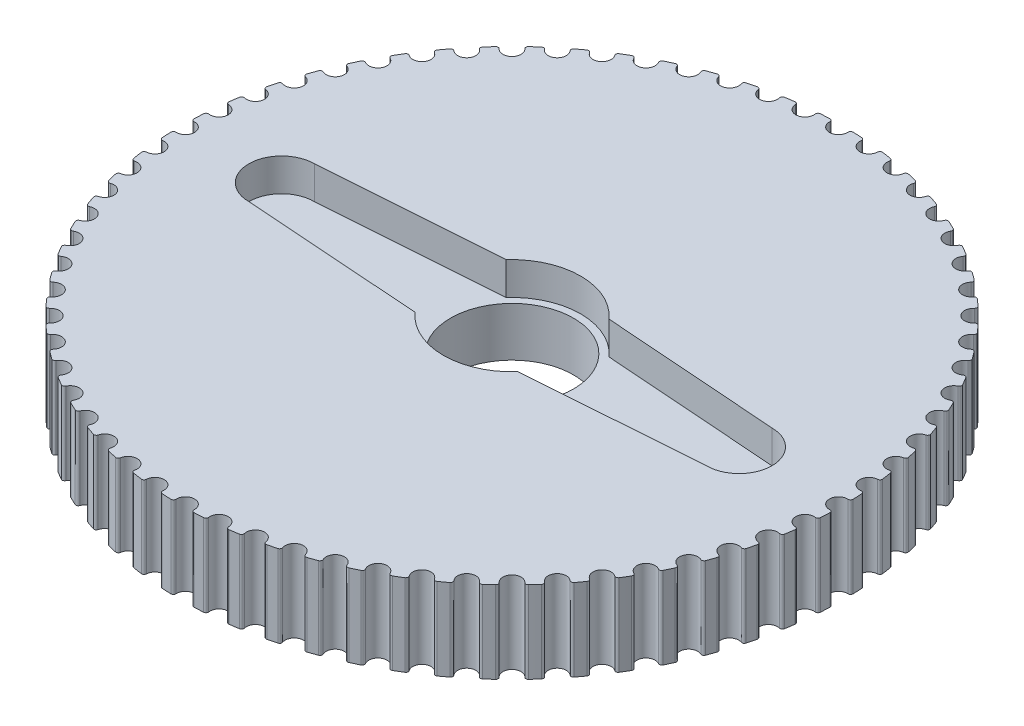
SolidWorks part; units mm, degrees
ref_plane "Front Plane" through (0, 0, 0) normal (0, 0, 1) x (1, 0, 0)
ref_plane "Top Plane" through (0, 0, 0) normal (0, 1, 0) x (1, 0, 0)
ref_plane "Right Plane" through (0, 0, 0) normal (1, 0, 0) x (0, 0, -1)
sketch "Sketch1" plane through (0, 0, 0) normal (0, 1, 0) x (1, 0, 0)
  line L1 (19.37, 0) -> (20.12, 0) construction
  arc A0 (1.2648, 20.0802) -> (0.7095, 20.1075) centre (0, 0) ccw
  arc A2 (0, 19.37) -> (0.5544, 19.9506) centre (0, 19.925) ccw
  arc A3 (1.4038, 19.9089) -> (1.8986, 19.2767) centre (1.953, 19.8291) ccw
  arc A4 (0.7095, 20.1075) -> (0.5544, 19.9506) centre (0.7042, 19.9576) ccw
  arc A5 (1.4038, 19.9089) -> (1.2648, 20.0802) centre (1.2553, 19.9305) ccw
  arc A6 (3.2269, 19.8595) -> (2.677, 19.9411) centre (0, 0) ccw
  arc A7 (1.8986, 19.2767) -> (2.5072, 19.8002) centre (1.953, 19.8291) ccw
  arc A8 (3.3484, 19.6755) -> (3.7789, 18.9978) centre (3.8872, 19.5421) ccw
  arc A9 (2.677, 19.9411) -> (2.5072, 19.8002) centre (2.657, 19.7924) ccw
  arc A10 (3.3484, 19.6755) -> (3.2269, 19.8595) centre (3.2028, 19.7115) ccw
  arc A11 (5.1579, 19.4476) -> (4.6187, 19.5827) centre (0, 0) ccw
  arc A12 (3.7789, 18.9978) -> (4.4359, 19.4591) centre (3.8872, 19.5421) ccw
  arc A13 (5.2608, 19.2525) -> (5.6228, 18.5359) centre (5.7839, 19.067) ccw
  arc A14 (4.6187, 19.5827) -> (4.4359, 19.4591) centre (4.5842, 19.4367) ccw
  arc A15 (5.2608, 19.2525) -> (5.1579, 19.4476) centre (5.1195, 19.3026) ccw
  arc A16 (7.0393, 18.8484) -> (6.5159, 19.0357) centre (0, 0) ccw
  arc A17 (5.6228, 18.5359) -> (6.3219, 18.9306) centre (5.7839, 19.067) ccw
  arc A18 (7.1226, 18.6442) -> (7.4126, 17.8955) centre (7.625, 18.4083) ccw
  arc A19 (6.5159, 19.0357) -> (6.3219, 18.9306) centre (6.4673, 18.8938) ccw
  arc A20 (7.1226, 18.6442) -> (7.0393, 18.8484) centre (6.9868, 18.7079) ccw
  arc A21 (8.8528, 18.0677) -> (8.3503, 18.3054) centre (0, 0) ccw
  arc A22 (7.4126, 17.8955) -> (8.147, 18.2198) centre (7.625, 18.4083) ccw
  arc A23 (8.9157, 17.8562) -> (9.131, 17.0828) centre (9.3926, 17.5723) ccw
  arc A24 (8.3503, 18.3054) -> (8.147, 18.2198) centre (8.2881, 18.1689) ccw
  arc A25 (8.9157, 17.8562) -> (8.8528, 18.0677) centre (8.7868, 17.933) ccw
  arc A26 (10.5812, 17.113) -> (10.1044, 17.3987) centre (0, 0) ccw
  arc A27 (9.131, 17.0828) -> (9.8936, 17.3336) centre (9.3926, 17.5723) ccw
  arc A28 (10.623, 16.8964) -> (10.7614, 16.1056) centre (11.0697, 16.567) ccw
  arc A29 (10.1044, 17.3987) -> (9.8936, 17.3336) centre (10.029, 17.269) ccw
  arc A30 (10.623, 16.8964) -> (10.5812, 17.113) centre (10.5023, 16.9854) ccw
  arc A31 (12.2076, 15.9934) -> (11.7611, 16.3246) centre (0, 0) ccw
  arc A32 (10.7614, 16.1056) -> (11.545, 16.2803) centre (11.0697, 16.567) ccw
  arc A33 (12.228, 15.7738) -> (12.2882, 14.9732) centre (12.6403, 15.4022) ccw
  arc A34 (11.7611, 16.3246) -> (11.545, 16.2803) centre (11.6734, 16.2029) ccw
  arc A35 (12.228, 15.7738) -> (12.2076, 15.9934) centre (12.1166, 15.8742) ccw
  arc A36 (13.7164, 14.7199) -> (13.3045, 15.0932) centre (0, 0) ccw
  arc A37 (12.2882, 14.9732) -> (13.0851, 15.0703) centre (12.6403, 15.4022) ccw
  arc A38 (13.7152, 14.4993) -> (13.6967, 13.6967) centre (14.0891, 14.0891) ccw
  arc A39 (13.3045, 15.0932) -> (13.0851, 15.0703) centre (13.2053, 14.9806) ccw
  arc A40 (13.7152, 14.4993) -> (13.7164, 14.7199) centre (13.6142, 14.6101) ccw
  arc A41 (15.0932, 13.3045) -> (14.7199, 13.7164) centre (0, 0) ccw
  arc A42 (13.6967, 13.6967) -> (14.4993, 13.7152) centre (14.0891, 14.0891) ccw
  arc A43 (15.0703, 13.0851) -> (14.9732, 12.2882) centre (15.4022, 12.6403) ccw
  arc A44 (14.7199, 13.7164) -> (14.4993, 13.7152) centre (14.6101, 13.6142) ccw
  arc A45 (15.0703, 13.0851) -> (15.0932, 13.3045) centre (14.9806, 13.2053) ccw
  arc A46 (16.3246, 11.7611) -> (15.9934, 12.2076) centre (0, 0) ccw
  arc A47 (14.9732, 12.2882) -> (15.7738, 12.228) centre (15.4022, 12.6403) ccw
  arc A48 (16.2803, 11.545) -> (16.1056, 10.7614) centre (16.567, 11.0697) ccw
  arc A49 (15.9934, 12.2076) -> (15.7738, 12.228) centre (15.8742, 12.1166) ccw
  arc A50 (16.2803, 11.545) -> (16.3246, 11.7611) centre (16.2029, 11.6734) ccw
  arc A51 (17.3987, 10.1044) -> (17.113, 10.5812) centre (0, 0) ccw
  arc A52 (16.1056, 10.7614) -> (16.8964, 10.623) centre (16.567, 11.0697) ccw
  arc A53 (17.3336, 9.8936) -> (17.0828, 9.131) centre (17.5723, 9.3926) ccw
  arc A54 (17.113, 10.5812) -> (16.8964, 10.623) centre (16.9854, 10.5023) ccw
  arc A55 (17.3336, 9.8936) -> (17.3987, 10.1044) centre (17.269, 10.029) ccw
  arc A56 (18.3054, 8.3503) -> (18.0677, 8.8528) centre (0, 0) ccw
  arc A57 (17.0828, 9.131) -> (17.8562, 8.9157) centre (17.5723, 9.3926) ccw
  arc A58 (18.2198, 8.147) -> (17.8955, 7.4126) centre (18.4083, 7.625) ccw
  arc A59 (18.0677, 8.8528) -> (17.8562, 8.9157) centre (17.933, 8.7868) ccw
  arc A60 (18.2198, 8.147) -> (18.3054, 8.3503) centre (18.1689, 8.2881) ccw
  arc A61 (19.0357, 6.5159) -> (18.8484, 7.0393) centre (0, 0) ccw
  arc A62 (17.8955, 7.4126) -> (18.6442, 7.1226) centre (18.4083, 7.625) ccw
  arc A63 (18.9306, 6.3219) -> (18.5359, 5.6228) centre (19.067, 5.7839) ccw
  arc A64 (18.8484, 7.0393) -> (18.6442, 7.1226) centre (18.7079, 6.9868) ccw
  arc A65 (18.9306, 6.3219) -> (19.0357, 6.5159) centre (18.8938, 6.4673) ccw
  arc A66 (19.5827, 4.6187) -> (19.4476, 5.1579) centre (0, 0) ccw
  arc A67 (18.5359, 5.6228) -> (19.2525, 5.2608) centre (19.067, 5.7839) ccw
  arc A68 (19.4591, 4.4359) -> (18.9978, 3.7789) centre (19.5421, 3.8872) ccw
  arc A69 (19.4476, 5.1579) -> (19.2525, 5.2608) centre (19.3026, 5.1195) ccw
  arc A70 (19.4591, 4.4359) -> (19.5827, 4.6187) centre (19.4367, 4.5842) ccw
  arc A71 (19.9411, 2.677) -> (19.8595, 3.2269) centre (0, 0) ccw
  arc A72 (18.9978, 3.7789) -> (19.6755, 3.3484) centre (19.5421, 3.8872) ccw
  arc A73 (19.8002, 2.5072) -> (19.2767, 1.8986) centre (19.8291, 1.953) ccw
  arc A74 (19.8595, 3.2269) -> (19.6755, 3.3484) centre (19.7115, 3.2028) ccw
  arc A75 (19.8002, 2.5072) -> (19.9411, 2.677) centre (19.7924, 2.657) ccw
  arc A76 (20.1075, 0.7095) -> (20.0802, 1.2648) centre (0, 0) ccw
  arc A77 (19.2767, 1.8986) -> (19.9089, 1.4038) centre (19.8291, 1.953) ccw
  arc A78 (19.9506, 0.5544) -> (19.37, 0) centre (19.925, 0) ccw
  arc A79 (20.0802, 1.2648) -> (19.9089, 1.4038) centre (19.9305, 1.2553) ccw
  arc A80 (19.9506, 0.5544) -> (20.1075, 0.7095) centre (19.9576, 0.7042) ccw
  arc A81 (20.0802, -1.2648) -> (20.1075, -0.7095) centre (0, 0) ccw
  arc A82 (19.37, 0) -> (19.9506, -0.5544) centre (19.925, 0) ccw
  arc A83 (19.9089, -1.4038) -> (19.2767, -1.8986) centre (19.8291, -1.953) ccw
  arc A84 (20.1075, -0.7095) -> (19.9506, -0.5544) centre (19.9576, -0.7042) ccw
  arc A85 (19.9089, -1.4038) -> (20.0802, -1.2648) centre (19.9305, -1.2553) ccw
  arc A86 (19.8595, -3.2269) -> (19.9411, -2.677) centre (0, 0) ccw
  arc A87 (19.2767, -1.8986) -> (19.8002, -2.5072) centre (19.8291, -1.953) ccw
  arc A88 (19.6755, -3.3484) -> (18.9978, -3.7789) centre (19.5421, -3.8872) ccw
  arc A89 (19.9411, -2.677) -> (19.8002, -2.5072) centre (19.7924, -2.657) ccw
  arc A90 (19.6755, -3.3484) -> (19.8595, -3.2269) centre (19.7115, -3.2028) ccw
  arc A91 (19.4476, -5.1579) -> (19.5827, -4.6187) centre (0, 0) ccw
  arc A92 (18.9978, -3.7789) -> (19.4591, -4.4359) centre (19.5421, -3.8872) ccw
  arc A93 (19.2525, -5.2608) -> (18.5359, -5.6228) centre (19.067, -5.7839) ccw
  arc A94 (19.5827, -4.6187) -> (19.4591, -4.4359) centre (19.4367, -4.5842) ccw
  arc A95 (19.2525, -5.2608) -> (19.4476, -5.1579) centre (19.3026, -5.1195) ccw
  arc A96 (18.8484, -7.0393) -> (19.0357, -6.5159) centre (0, 0) ccw
  arc A97 (18.5359, -5.6228) -> (18.9306, -6.3219) centre (19.067, -5.7839) ccw
  arc A98 (18.6442, -7.1226) -> (17.8955, -7.4126) centre (18.4083, -7.625) ccw
  arc A99 (19.0357, -6.5159) -> (18.9306, -6.3219) centre (18.8938, -6.4673) ccw
  arc A100 (18.6442, -7.1226) -> (18.8484, -7.0393) centre (18.7079, -6.9868) ccw
  arc A101 (18.0677, -8.8528) -> (18.3054, -8.3503) centre (0, 0) ccw
  arc A102 (17.8955, -7.4126) -> (18.2198, -8.147) centre (18.4083, -7.625) ccw
  arc A103 (17.8562, -8.9157) -> (17.0828, -9.131) centre (17.5723, -9.3926) ccw
  arc A104 (18.3054, -8.3503) -> (18.2198, -8.147) centre (18.1689, -8.2881) ccw
  arc A105 (17.8562, -8.9157) -> (18.0677, -8.8528) centre (17.933, -8.7868) ccw
  arc A106 (17.113, -10.5812) -> (17.3987, -10.1044) centre (0, 0) ccw
  arc A107 (17.0828, -9.131) -> (17.3336, -9.8936) centre (17.5723, -9.3926) ccw
  arc A108 (16.8964, -10.623) -> (16.1056, -10.7614) centre (16.567, -11.0697) ccw
  arc A109 (17.3987, -10.1044) -> (17.3336, -9.8936) centre (17.269, -10.029) ccw
  arc A110 (16.8964, -10.623) -> (17.113, -10.5812) centre (16.9854, -10.5023) ccw
  arc A111 (15.9934, -12.2076) -> (16.3246, -11.7611) centre (0, 0) ccw
  arc A112 (16.1056, -10.7614) -> (16.2803, -11.545) centre (16.567, -11.0697) ccw
  arc A113 (15.7738, -12.228) -> (14.9732, -12.2882) centre (15.4022, -12.6403) ccw
  arc A114 (16.3246, -11.7611) -> (16.2803, -11.545) centre (16.2029, -11.6734) ccw
  arc A115 (15.7738, -12.228) -> (15.9934, -12.2076) centre (15.8742, -12.1166) ccw
  arc A116 (14.7199, -13.7164) -> (15.0932, -13.3045) centre (0, 0) ccw
  arc A117 (14.9732, -12.2882) -> (15.0703, -13.0851) centre (15.4022, -12.6403) ccw
  arc A118 (14.4993, -13.7152) -> (13.6967, -13.6967) centre (14.0891, -14.0891) ccw
  arc A119 (15.0932, -13.3045) -> (15.0703, -13.0851) centre (14.9806, -13.2053) ccw
  arc A120 (14.4993, -13.7152) -> (14.7199, -13.7164) centre (14.6101, -13.6142) ccw
  arc A121 (13.3045, -15.0932) -> (13.7164, -14.7199) centre (0, 0) ccw
  arc A122 (13.6967, -13.6967) -> (13.7152, -14.4993) centre (14.0891, -14.0891) ccw
  arc A123 (13.0851, -15.0703) -> (12.2882, -14.9732) centre (12.6403, -15.4022) ccw
  arc A124 (13.7164, -14.7199) -> (13.7152, -14.4993) centre (13.6142, -14.6101) ccw
  arc A125 (13.0851, -15.0703) -> (13.3045, -15.0932) centre (13.2053, -14.9806) ccw
  arc A126 (11.7611, -16.3246) -> (12.2076, -15.9934) centre (0, 0) ccw
  arc A127 (12.2882, -14.9732) -> (12.228, -15.7738) centre (12.6403, -15.4022) ccw
  arc A128 (11.545, -16.2803) -> (10.7614, -16.1056) centre (11.0697, -16.567) ccw
  arc A129 (12.2076, -15.9934) -> (12.228, -15.7738) centre (12.1166, -15.8742) ccw
  arc A130 (11.545, -16.2803) -> (11.7611, -16.3246) centre (11.6734, -16.2029) ccw
  arc A131 (10.1044, -17.3987) -> (10.5812, -17.113) centre (0, 0) ccw
  arc A132 (10.7614, -16.1056) -> (10.623, -16.8964) centre (11.0697, -16.567) ccw
  arc A133 (9.8936, -17.3336) -> (9.131, -17.0828) centre (9.3926, -17.5723) ccw
  arc A134 (10.5812, -17.113) -> (10.623, -16.8964) centre (10.5023, -16.9854) ccw
  arc A135 (9.8936, -17.3336) -> (10.1044, -17.3987) centre (10.029, -17.269) ccw
  arc A136 (8.3503, -18.3054) -> (8.8528, -18.0677) centre (0, 0) ccw
  arc A137 (9.131, -17.0828) -> (8.9157, -17.8562) centre (9.3926, -17.5723) ccw
  arc A138 (8.147, -18.2198) -> (7.4126, -17.8955) centre (7.625, -18.4083) ccw
  arc A139 (8.8528, -18.0677) -> (8.9157, -17.8562) centre (8.7868, -17.933) ccw
  arc A140 (8.147, -18.2198) -> (8.3503, -18.3054) centre (8.2881, -18.1689) ccw
  arc A141 (6.5159, -19.0357) -> (7.0393, -18.8484) centre (0, 0) ccw
  arc A142 (7.4126, -17.8955) -> (7.1226, -18.6442) centre (7.625, -18.4083) ccw
  arc A143 (6.3219, -18.9306) -> (5.6228, -18.5359) centre (5.7839, -19.067) ccw
  arc A144 (7.0393, -18.8484) -> (7.1226, -18.6442) centre (6.9868, -18.7079) ccw
  arc A145 (6.3219, -18.9306) -> (6.5159, -19.0357) centre (6.4673, -18.8938) ccw
  arc A146 (4.6187, -19.5827) -> (5.1579, -19.4476) centre (0, 0) ccw
  arc A147 (5.6228, -18.5359) -> (5.2608, -19.2525) centre (5.7839, -19.067) ccw
  arc A148 (4.4359, -19.4591) -> (3.7789, -18.9978) centre (3.8872, -19.5421) ccw
  arc A149 (5.1579, -19.4476) -> (5.2608, -19.2525) centre (5.1195, -19.3026) ccw
  arc A150 (4.4359, -19.4591) -> (4.6187, -19.5827) centre (4.5842, -19.4367) ccw
  arc A151 (2.677, -19.9411) -> (3.2269, -19.8595) centre (0, 0) ccw
  arc A152 (3.7789, -18.9978) -> (3.3484, -19.6755) centre (3.8872, -19.5421) ccw
  arc A153 (2.5072, -19.8002) -> (1.8986, -19.2767) centre (1.953, -19.8291) ccw
  arc A154 (3.2269, -19.8595) -> (3.3484, -19.6755) centre (3.2028, -19.7115) ccw
  arc A155 (2.5072, -19.8002) -> (2.677, -19.9411) centre (2.657, -19.7924) ccw
  arc A156 (0.7095, -20.1075) -> (1.2648, -20.0802) centre (0, 0) ccw
  arc A157 (1.8986, -19.2767) -> (1.4038, -19.9089) centre (1.953, -19.8291) ccw
  arc A158 (0.5544, -19.9506) -> (0, -19.37) centre (0, -19.925) ccw
  arc A159 (1.2648, -20.0802) -> (1.4038, -19.9089) centre (1.2553, -19.9305) ccw
  arc A160 (0.5544, -19.9506) -> (0.7095, -20.1075) centre (0.7042, -19.9576) ccw
  arc A161 (-1.2648, -20.0802) -> (-0.7095, -20.1075) centre (0, 0) ccw
  arc A162 (0, -19.37) -> (-0.5544, -19.9506) centre (0, -19.925) ccw
  arc A163 (-1.4038, -19.9089) -> (-1.8986, -19.2767) centre (-1.953, -19.8291) ccw
  arc A164 (-0.7095, -20.1075) -> (-0.5544, -19.9506) centre (-0.7042, -19.9576) ccw
  arc A165 (-1.4038, -19.9089) -> (-1.2648, -20.0802) centre (-1.2553, -19.9305) ccw
  arc A166 (-3.2269, -19.8595) -> (-2.677, -19.9411) centre (0, 0) ccw
  arc A167 (-1.8986, -19.2767) -> (-2.5072, -19.8002) centre (-1.953, -19.8291) ccw
  arc A168 (-3.3484, -19.6755) -> (-3.7789, -18.9978) centre (-3.8872, -19.5421) ccw
  arc A169 (-2.677, -19.9411) -> (-2.5072, -19.8002) centre (-2.657, -19.7924) ccw
  arc A170 (-3.3484, -19.6755) -> (-3.2269, -19.8595) centre (-3.2028, -19.7115) ccw
  arc A171 (-5.1579, -19.4476) -> (-4.6187, -19.5827) centre (0, 0) ccw
  arc A172 (-3.7789, -18.9978) -> (-4.4359, -19.4591) centre (-3.8872, -19.5421) ccw
  arc A173 (-5.2608, -19.2525) -> (-5.6228, -18.5359) centre (-5.7839, -19.067) ccw
  arc A174 (-4.6187, -19.5827) -> (-4.4359, -19.4591) centre (-4.5842, -19.4367) ccw
  arc A175 (-5.2608, -19.2525) -> (-5.1579, -19.4476) centre (-5.1195, -19.3026) ccw
  arc A176 (-7.0393, -18.8484) -> (-6.5159, -19.0357) centre (0, 0) ccw
  arc A177 (-5.6228, -18.5359) -> (-6.3219, -18.9306) centre (-5.7839, -19.067) ccw
  arc A178 (-7.1226, -18.6442) -> (-7.4126, -17.8955) centre (-7.625, -18.4083) ccw
  arc A179 (-6.5159, -19.0357) -> (-6.3219, -18.9306) centre (-6.4673, -18.8938) ccw
  arc A180 (-7.1226, -18.6442) -> (-7.0393, -18.8484) centre (-6.9868, -18.7079) ccw
  arc A181 (-8.8528, -18.0677) -> (-8.3503, -18.3054) centre (0, 0) ccw
  arc A182 (-7.4126, -17.8955) -> (-8.147, -18.2198) centre (-7.625, -18.4083) ccw
  arc A183 (-8.9157, -17.8562) -> (-9.131, -17.0828) centre (-9.3926, -17.5723) ccw
  arc A184 (-8.3503, -18.3054) -> (-8.147, -18.2198) centre (-8.2881, -18.1689) ccw
  arc A185 (-8.9157, -17.8562) -> (-8.8528, -18.0677) centre (-8.7868, -17.933) ccw
  arc A186 (-10.5812, -17.113) -> (-10.1044, -17.3987) centre (0, 0) ccw
  arc A187 (-9.131, -17.0828) -> (-9.8936, -17.3336) centre (-9.3926, -17.5723) ccw
  arc A188 (-10.623, -16.8964) -> (-10.7614, -16.1056) centre (-11.0697, -16.567) ccw
  arc A189 (-10.1044, -17.3987) -> (-9.8936, -17.3336) centre (-10.029, -17.269) ccw
  arc A190 (-10.623, -16.8964) -> (-10.5812, -17.113) centre (-10.5023, -16.9854) ccw
  arc A191 (-12.2076, -15.9934) -> (-11.7611, -16.3246) centre (0, 0) ccw
  arc A192 (-10.7614, -16.1056) -> (-11.545, -16.2803) centre (-11.0697, -16.567) ccw
  arc A193 (-12.228, -15.7738) -> (-12.2882, -14.9732) centre (-12.6403, -15.4022) ccw
  arc A194 (-11.7611, -16.3246) -> (-11.545, -16.2803) centre (-11.6734, -16.2029) ccw
  arc A195 (-12.228, -15.7738) -> (-12.2076, -15.9934) centre (-12.1166, -15.8742) ccw
  arc A196 (-13.7164, -14.7199) -> (-13.3045, -15.0932) centre (0, 0) ccw
  arc A197 (-12.2882, -14.9732) -> (-13.0851, -15.0703) centre (-12.6403, -15.4022) ccw
  arc A198 (-13.7152, -14.4993) -> (-13.6967, -13.6967) centre (-14.0891, -14.0891) ccw
  arc A199 (-13.3045, -15.0932) -> (-13.0851, -15.0703) centre (-13.2053, -14.9806) ccw
  arc A200 (-13.7152, -14.4993) -> (-13.7164, -14.7199) centre (-13.6142, -14.6101) ccw
  arc A201 (-15.0932, -13.3045) -> (-14.7199, -13.7164) centre (0, 0) ccw
  arc A202 (-13.6967, -13.6967) -> (-14.4993, -13.7152) centre (-14.0891, -14.0891) ccw
  arc A203 (-15.0703, -13.0851) -> (-14.9732, -12.2882) centre (-15.4022, -12.6403) ccw
  arc A204 (-14.7199, -13.7164) -> (-14.4993, -13.7152) centre (-14.6101, -13.6142) ccw
  arc A205 (-15.0703, -13.0851) -> (-15.0932, -13.3045) centre (-14.9806, -13.2053) ccw
  arc A206 (-16.3246, -11.7611) -> (-15.9934, -12.2076) centre (0, 0) ccw
  arc A207 (-14.9732, -12.2882) -> (-15.7738, -12.228) centre (-15.4022, -12.6403) ccw
  arc A208 (-16.2803, -11.545) -> (-16.1056, -10.7614) centre (-16.567, -11.0697) ccw
  arc A209 (-15.9934, -12.2076) -> (-15.7738, -12.228) centre (-15.8742, -12.1166) ccw
  arc A210 (-16.2803, -11.545) -> (-16.3246, -11.7611) centre (-16.2029, -11.6734) ccw
  arc A211 (-17.3987, -10.1044) -> (-17.113, -10.5812) centre (0, 0) ccw
  arc A212 (-16.1056, -10.7614) -> (-16.8964, -10.623) centre (-16.567, -11.0697) ccw
  arc A213 (-17.3336, -9.8936) -> (-17.0828, -9.131) centre (-17.5723, -9.3926) ccw
  arc A214 (-17.113, -10.5812) -> (-16.8964, -10.623) centre (-16.9854, -10.5023) ccw
  arc A215 (-17.3336, -9.8936) -> (-17.3987, -10.1044) centre (-17.269, -10.029) ccw
  arc A216 (-18.3054, -8.3503) -> (-18.0677, -8.8528) centre (0, 0) ccw
  arc A217 (-17.0828, -9.131) -> (-17.8562, -8.9157) centre (-17.5723, -9.3926) ccw
  arc A218 (-18.2198, -8.147) -> (-17.8955, -7.4126) centre (-18.4083, -7.625) ccw
  arc A219 (-18.0677, -8.8528) -> (-17.8562, -8.9157) centre (-17.933, -8.7868) ccw
  arc A220 (-18.2198, -8.147) -> (-18.3054, -8.3503) centre (-18.1689, -8.2881) ccw
  arc A221 (-19.0357, -6.5159) -> (-18.8484, -7.0393) centre (0, 0) ccw
  arc A222 (-17.8955, -7.4126) -> (-18.6442, -7.1226) centre (-18.4083, -7.625) ccw
  arc A223 (-18.9306, -6.3219) -> (-18.5359, -5.6228) centre (-19.067, -5.7839) ccw
  arc A224 (-18.8484, -7.0393) -> (-18.6442, -7.1226) centre (-18.7079, -6.9868) ccw
  arc A225 (-18.9306, -6.3219) -> (-19.0357, -6.5159) centre (-18.8938, -6.4673) ccw
  arc A226 (-19.5827, -4.6187) -> (-19.4476, -5.1579) centre (0, 0) ccw
  arc A227 (-18.5359, -5.6228) -> (-19.2525, -5.2608) centre (-19.067, -5.7839) ccw
  arc A228 (-19.4591, -4.4359) -> (-18.9978, -3.7789) centre (-19.5421, -3.8872) ccw
  arc A229 (-19.4476, -5.1579) -> (-19.2525, -5.2608) centre (-19.3026, -5.1195) ccw
  arc A230 (-19.4591, -4.4359) -> (-19.5827, -4.6187) centre (-19.4367, -4.5842) ccw
  arc A231 (-19.9411, -2.677) -> (-19.8595, -3.2269) centre (0, 0) ccw
  arc A232 (-18.9978, -3.7789) -> (-19.6755, -3.3484) centre (-19.5421, -3.8872) ccw
  arc A233 (-19.8002, -2.5072) -> (-19.2767, -1.8986) centre (-19.8291, -1.953) ccw
  arc A234 (-19.8595, -3.2269) -> (-19.6755, -3.3484) centre (-19.7115, -3.2028) ccw
  arc A235 (-19.8002, -2.5072) -> (-19.9411, -2.677) centre (-19.7924, -2.657) ccw
  arc A236 (-20.1075, -0.7095) -> (-20.0802, -1.2648) centre (0, 0) ccw
  arc A237 (-19.2767, -1.8986) -> (-19.9089, -1.4038) centre (-19.8291, -1.953) ccw
  arc A238 (-19.9506, -0.5544) -> (-19.37, 0) centre (-19.925, 0) ccw
  arc A239 (-20.0802, -1.2648) -> (-19.9089, -1.4038) centre (-19.9305, -1.2553) ccw
  arc A240 (-19.9506, -0.5544) -> (-20.1075, -0.7095) centre (-19.9576, -0.7042) ccw
  arc A241 (-20.0802, 1.2648) -> (-20.1075, 0.7095) centre (0, 0) ccw
  arc A242 (-19.37, 0) -> (-19.9506, 0.5544) centre (-19.925, 0) ccw
  arc A243 (-19.9089, 1.4038) -> (-19.2767, 1.8986) centre (-19.8291, 1.953) ccw
  arc A244 (-20.1075, 0.7095) -> (-19.9506, 0.5544) centre (-19.9576, 0.7042) ccw
  arc A245 (-19.9089, 1.4038) -> (-20.0802, 1.2648) centre (-19.9305, 1.2553) ccw
  arc A246 (-19.8595, 3.2269) -> (-19.9411, 2.677) centre (0, 0) ccw
  arc A247 (-19.2767, 1.8986) -> (-19.8002, 2.5072) centre (-19.8291, 1.953) ccw
  arc A248 (-19.6755, 3.3484) -> (-18.9978, 3.7789) centre (-19.5421, 3.8872) ccw
  arc A249 (-19.9411, 2.677) -> (-19.8002, 2.5072) centre (-19.7924, 2.657) ccw
  arc A250 (-19.6755, 3.3484) -> (-19.8595, 3.2269) centre (-19.7115, 3.2028) ccw
  arc A251 (-19.4476, 5.1579) -> (-19.5827, 4.6187) centre (0, 0) ccw
  arc A252 (-18.9978, 3.7789) -> (-19.4591, 4.4359) centre (-19.5421, 3.8872) ccw
  arc A253 (-19.2525, 5.2608) -> (-18.5359, 5.6228) centre (-19.067, 5.7839) ccw
  arc A254 (-19.5827, 4.6187) -> (-19.4591, 4.4359) centre (-19.4367, 4.5842) ccw
  arc A255 (-19.2525, 5.2608) -> (-19.4476, 5.1579) centre (-19.3026, 5.1195) ccw
  arc A256 (-18.8484, 7.0393) -> (-19.0357, 6.5159) centre (0, 0) ccw
  arc A257 (-18.5359, 5.6228) -> (-18.9306, 6.3219) centre (-19.067, 5.7839) ccw
  arc A258 (-18.6442, 7.1226) -> (-17.8955, 7.4126) centre (-18.4083, 7.625) ccw
  arc A259 (-19.0357, 6.5159) -> (-18.9306, 6.3219) centre (-18.8938, 6.4673) ccw
  arc A260 (-18.6442, 7.1226) -> (-18.8484, 7.0393) centre (-18.7079, 6.9868) ccw
  arc A261 (-18.0677, 8.8528) -> (-18.3054, 8.3503) centre (0, 0) ccw
  arc A262 (-17.8955, 7.4126) -> (-18.2198, 8.147) centre (-18.4083, 7.625) ccw
  arc A263 (-17.8562, 8.9157) -> (-17.0828, 9.131) centre (-17.5723, 9.3926) ccw
  arc A264 (-18.3054, 8.3503) -> (-18.2198, 8.147) centre (-18.1689, 8.2881) ccw
  arc A265 (-17.8562, 8.9157) -> (-18.0677, 8.8528) centre (-17.933, 8.7868) ccw
  arc A266 (-17.113, 10.5812) -> (-17.3987, 10.1044) centre (0, 0) ccw
  arc A267 (-17.0828, 9.131) -> (-17.3336, 9.8936) centre (-17.5723, 9.3926) ccw
  arc A268 (-16.8964, 10.623) -> (-16.1056, 10.7614) centre (-16.567, 11.0697) ccw
  arc A269 (-17.3987, 10.1044) -> (-17.3336, 9.8936) centre (-17.269, 10.029) ccw
  arc A270 (-16.8964, 10.623) -> (-17.113, 10.5812) centre (-16.9854, 10.5023) ccw
  arc A271 (-15.9934, 12.2076) -> (-16.3246, 11.7611) centre (0, 0) ccw
  arc A272 (-16.1056, 10.7614) -> (-16.2803, 11.545) centre (-16.567, 11.0697) ccw
  arc A273 (-15.7738, 12.228) -> (-14.9732, 12.2882) centre (-15.4022, 12.6403) ccw
  arc A274 (-16.3246, 11.7611) -> (-16.2803, 11.545) centre (-16.2029, 11.6734) ccw
  arc A275 (-15.7738, 12.228) -> (-15.9934, 12.2076) centre (-15.8742, 12.1166) ccw
  arc A276 (-14.7199, 13.7164) -> (-15.0932, 13.3045) centre (0, 0) ccw
  arc A277 (-14.9732, 12.2882) -> (-15.0703, 13.0851) centre (-15.4022, 12.6403) ccw
  arc A278 (-14.4993, 13.7152) -> (-13.6967, 13.6967) centre (-14.0891, 14.0891) ccw
  arc A279 (-15.0932, 13.3045) -> (-15.0703, 13.0851) centre (-14.9806, 13.2053) ccw
  arc A280 (-14.4993, 13.7152) -> (-14.7199, 13.7164) centre (-14.6101, 13.6142) ccw
  arc A281 (-13.3045, 15.0932) -> (-13.7164, 14.7199) centre (0, 0) ccw
  arc A282 (-13.6967, 13.6967) -> (-13.7152, 14.4993) centre (-14.0891, 14.0891) ccw
  arc A283 (-13.0851, 15.0703) -> (-12.2882, 14.9732) centre (-12.6403, 15.4022) ccw
  arc A284 (-13.7164, 14.7199) -> (-13.7152, 14.4993) centre (-13.6142, 14.6101) ccw
  arc A285 (-13.0851, 15.0703) -> (-13.3045, 15.0932) centre (-13.2053, 14.9806) ccw
  arc A286 (-11.7611, 16.3246) -> (-12.2076, 15.9934) centre (0, 0) ccw
  arc A287 (-12.2882, 14.9732) -> (-12.228, 15.7738) centre (-12.6403, 15.4022) ccw
  arc A288 (-11.545, 16.2803) -> (-10.7614, 16.1056) centre (-11.0697, 16.567) ccw
  arc A289 (-12.2076, 15.9934) -> (-12.228, 15.7738) centre (-12.1166, 15.8742) ccw
  arc A290 (-11.545, 16.2803) -> (-11.7611, 16.3246) centre (-11.6734, 16.2029) ccw
  arc A291 (-10.1044, 17.3987) -> (-10.5812, 17.113) centre (0, 0) ccw
  arc A292 (-10.7614, 16.1056) -> (-10.623, 16.8964) centre (-11.0697, 16.567) ccw
  arc A293 (-9.8936, 17.3336) -> (-9.131, 17.0828) centre (-9.3926, 17.5723) ccw
  arc A294 (-10.5812, 17.113) -> (-10.623, 16.8964) centre (-10.5023, 16.9854) ccw
  arc A295 (-9.8936, 17.3336) -> (-10.1044, 17.3987) centre (-10.029, 17.269) ccw
  arc A296 (-8.3503, 18.3054) -> (-8.8528, 18.0677) centre (0, 0) ccw
  arc A297 (-9.131, 17.0828) -> (-8.9157, 17.8562) centre (-9.3926, 17.5723) ccw
  arc A298 (-8.147, 18.2198) -> (-7.4126, 17.8955) centre (-7.625, 18.4083) ccw
  arc A299 (-8.8528, 18.0677) -> (-8.9157, 17.8562) centre (-8.7868, 17.933) ccw
  arc A300 (-8.147, 18.2198) -> (-8.3503, 18.3054) centre (-8.2881, 18.1689) ccw
  arc A301 (-6.5159, 19.0357) -> (-7.0393, 18.8484) centre (0, 0) ccw
  arc A302 (-7.4126, 17.8955) -> (-7.1226, 18.6442) centre (-7.625, 18.4083) ccw
  arc A303 (-6.3219, 18.9306) -> (-5.6228, 18.5359) centre (-5.7839, 19.067) ccw
  arc A304 (-7.0393, 18.8484) -> (-7.1226, 18.6442) centre (-6.9868, 18.7079) ccw
  arc A305 (-6.3219, 18.9306) -> (-6.5159, 19.0357) centre (-6.4673, 18.8938) ccw
  arc A306 (-4.6187, 19.5827) -> (-5.1579, 19.4476) centre (0, 0) ccw
  arc A307 (-5.6228, 18.5359) -> (-5.2608, 19.2525) centre (-5.7839, 19.067) ccw
  arc A308 (-4.4359, 19.4591) -> (-3.7789, 18.9978) centre (-3.8872, 19.5421) ccw
  arc A309 (-5.1579, 19.4476) -> (-5.2608, 19.2525) centre (-5.1195, 19.3026) ccw
  arc A310 (-4.4359, 19.4591) -> (-4.6187, 19.5827) centre (-4.5842, 19.4367) ccw
  arc A311 (-2.677, 19.9411) -> (-3.2269, 19.8595) centre (0, 0) ccw
  arc A312 (-3.7789, 18.9978) -> (-3.3484, 19.6755) centre (-3.8872, 19.5421) ccw
  arc A313 (-2.5072, 19.8002) -> (-1.8986, 19.2767) centre (-1.953, 19.8291) ccw
  arc A314 (-3.2269, 19.8595) -> (-3.3484, 19.6755) centre (-3.2028, 19.7115) ccw
  arc A315 (-2.5072, 19.8002) -> (-2.677, 19.9411) centre (-2.657, 19.7924) ccw
  arc A316 (-0.7095, 20.1075) -> (-1.2648, 20.0802) centre (0, 0) ccw
  arc A317 (-1.8986, 19.2767) -> (-1.4038, 19.9089) centre (-1.953, 19.8291) ccw
  arc A318 (-0.5544, 19.9506) -> (0, 19.37) centre (0, 19.925) ccw
  arc A319 (-1.2648, 20.0802) -> (-1.4038, 19.9089) centre (-1.2553, 19.9305) ccw
  arc A320 (-0.5544, 19.9506) -> (-0.7095, 20.1075) centre (-0.7042, 19.9576) ccw
extrude "Boss-Extrude1" add sketch "Sketch1" along normal blind 5
sketch "Sketch2" plane through (0, 5, 0) normal (0, 1, 0) x (1, 0, 0)
  line L4 (-3.1413, -2.7756) -> (-14.0585, -2)
  line L5 (3.1361, 2.7814) -> (13.8624, 2)
  line L6 (3.1413, -2.7756) -> (13.8624, -2)
  line L7 (-3.1361, 2.7814) -> (-14.0585, 2)
  arc A0 (-3.1413, -2.7756) -> (3.1413, -2.7756) centre (0, 0) ccw
  arc A2 (13.8624, -2) -> (13.8624, 2) centre (13.8624, 0) ccw
  arc A3 (-14.0585, -2) -> (-14.0585, 2) centre (-14.0585, 0) cw
  arc A4 (3.1361, 2.7814) -> (-3.1361, 2.7814) centre (0, 0) ccw
extrude "Cut-Extrude2" cut sketch "Sketch2" against normal blind 2
sketch "Sketch4" plane through (0, 3, 0) normal (0, 1, 0) x (1, 0, 0)
  circle A0 centre (0, 0) radius 3.75
extrude "Cut-Extrude3" cut sketch "Sketch4" against normal blind 3
